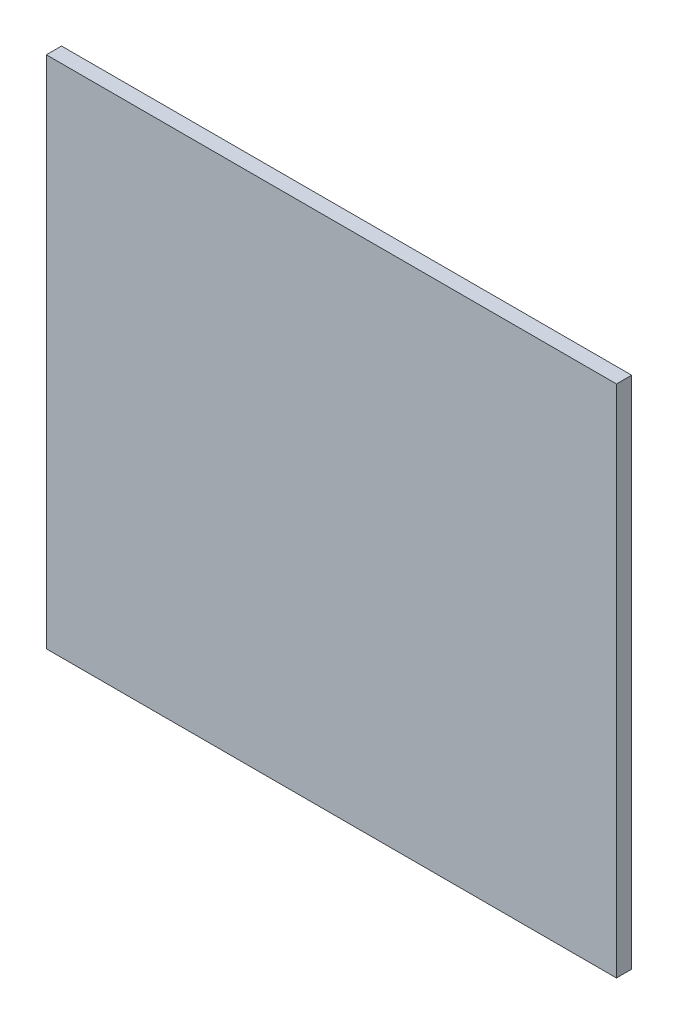
SolidWorks part; units mm, degrees
ref_plane "Front Plane" through (0, 0, 0) normal (0, 0, 1) x (1, 0, 0)
ref_plane "Top Plane" through (0, 0, 0) normal (0, 1, 0) x (1, 0, 0)
ref_plane "Right Plane" through (0, 0, 0) normal (1, 0, 0) x (0, 0, -1)
sketch "Sketch1" plane through (0, 0, 0) normal (0, 0, 1) x (1, 0, 0)
  line L1 (-169, -152.5) -> (169, -152.5)
  line L2 (-169, -152.5) -> (-169, 152.5)
  line L3 (-169, 152.5) -> (169, 152.5)
  line L4 (169, -152.5) -> (169, 152.5)
  line L5 (-169, -152.5) -> (169, 152.5) construction
  line L6 (-169, 152.5) -> (169, -152.5) construction
  point P0 (0, 0)
  dimension "D1" = 338
  dimension "D2" = 305
extrude "Boss-Extrude1" add sketch "Sketch1" along normal blind 9
equation "\"PCLength\"= 320mm'Length across I/O from PS to GPU"
equation "\"PCWidth\"= 242mm'Distance of longest part parallel to GPU(ussually GPU)"
equation "\"PCHeight\"= 172mm'Tallest point with mobo laying flat"
equation "\"WallThickness\"= 9mm'Thickness of each outer tank wall"
equation "\"ThermoBarrierThickness\"= 3mm'Thickness of barrier between hot side and cold side"
equation "\"HotSideGap\"= 35mm'Space in the hot side for a pump"
equation "\"PCClearance\"= 30mm'Clearance from top of tank to top of PC"
equation "\"RadiatorHeight\"= 275mm'Final Height from ground of radiators"
equation "\"D1@Sketch1\"=\"PCLength\" + (2 * \"WallThickness\")"
equation "\"D2@Sketch1\"=\"RadiatorHeight\" + \"PCClearance\""
equation "\"D1@Boss-Extrude1\"=\"WallThickness\""
